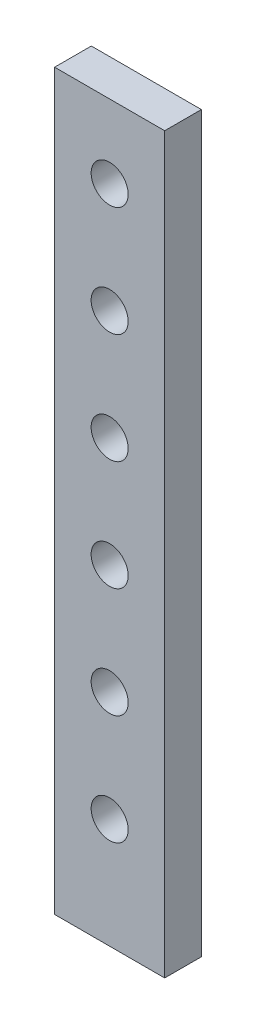
SolidWorks part; units mm, degrees
ref_plane "Спереди" through (0, 0, 0) normal (0, 0, 1) x (1, 0, 0)
ref_plane "Сверху" through (0, 0, 0) normal (0, 1, 0) x (1, 0, 0)
ref_plane "Справа" through (0, 0, 0) normal (1, 0, 0) x (0, 0, -1)
sketch "Эскиз1" plane through (0, 0, 0) normal (0, 0, 1) x (1, 0, 0)
  line L1 (0, 0) -> (30, 0)
  line L2 (0, 0) -> (0, 200)
  line L3 (0, 200) -> (30, 200)
  line L4 (30, 0) -> (30, 200)
extrude "Бобышка-Вытянуть1" add sketch "Эскиз1" along normal blind 10
sketch "Эскиз2" plane through (0, 0, 10) normal (0, 0, 1) x (1, 0, 0)
  circle A0 centre (15, 30) radius 5.05
  circle A1 centre (15, 60) radius 5.05
  circle A2 centre (15, 90) radius 5.05
  circle A3 centre (15, 120) radius 5.05
  circle A4 centre (15, 150) radius 5.05
  circle A5 centre (15, 180) radius 5.05
  dimension "D1" = 6
extrude "Вырез-Вытянуть1" cut sketch "Эскиз2" against normal through all
